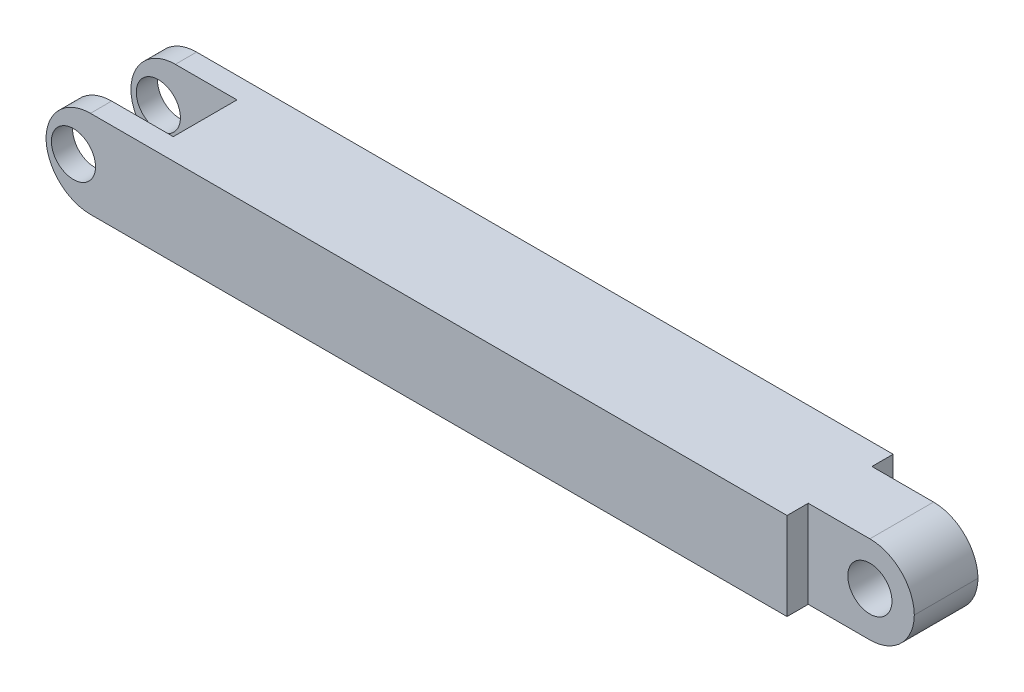
SolidWorks part; units mm, degrees
ref_plane "Front Plane" through (0, 0, 0) normal (0, 0, 1) x (1, 0, 0)
ref_plane "Top Plane" through (0, 0, 0) normal (0, 1, 0) x (1, 0, 0)
ref_plane "Right Plane" through (0, 0, 0) normal (1, 0, 0) x (0, 0, -1)
sketch "Sketch1" plane through (0, 0, 0) normal (0, 1, 0) x (1, 0, 0)
  line L0 (0, 0) -> (69.85, 0)
  line L1 (0, 0) -> (0, -1.999)
  line L2 (0, -1.999) -> (10, -1.999)
  line L3 (0, 0) -> (0, -1.999)
  line L4 (0, -10) -> (0, -8.001)
  line L5 (0, -8.001) -> (10, -8.001)
  line L6 (10, -8.001) -> (10, -1.999)
  line L7 (0, -10) -> (69.85, -10)
  line L8 (0, -8.001) -> (0, -10)
  line L10 (69.85, 0) -> (69.85, -1.999)
  line L11 (69.85, -1.999) -> (79.85, -1.999)
  line L12 (79.85, -1.999) -> (79.85, -8.001)
  line L13 (79.85, -8.001) -> (69.85, -8.001)
  line L14 (69.85, -8.001) -> (69.85, -10)
  dimension "D1" = 69.85
  dimension "D2" = 1.999
  dimension "D3" = 10
  dimension "D4" = 10
  dimension "D5" = 1.999
  dimension "D6" = 69.85
extrude "Boss-Extrude1" add sketch "Sketch1" along normal blind 8.255 contours L14 L13 L12 L11 L10 L0 L1 L2 L6 L5 L4 L7 region at (40.927, 0, 5)
fillet "Fillet1" radius 4.191 4 edges at (0, 0, 0.9995) (0, 0, 9.0005) (0, 8.255, 0.9995) (0, 8.255, 9.0005)
sketch "Sketch2" plane through (0, 0, 10) normal (0, 0, 1) x (1, 0, 0)
  circle A1 centre (2.5875, 4.1275) radius 2.079
  dimension "D2" = 4.158
extrude "Cut-Extrude1" cut sketch "Sketch2" against normal through all
fillet "Fillet2" radius 4.191 2 edges at (79.85, 0, 5) (79.85, 8.255, 5)
sketch "Sketch3" plane through (0, 0, 8.001) normal (0, 0, 1) x (1, 0, 0)
  circle A0 centre (75.659, 4.191) radius 2.079
  dimension "D1" = 4.158
extrude "Cut-Extrude2" cut sketch "Sketch3" against normal blind 8.255
